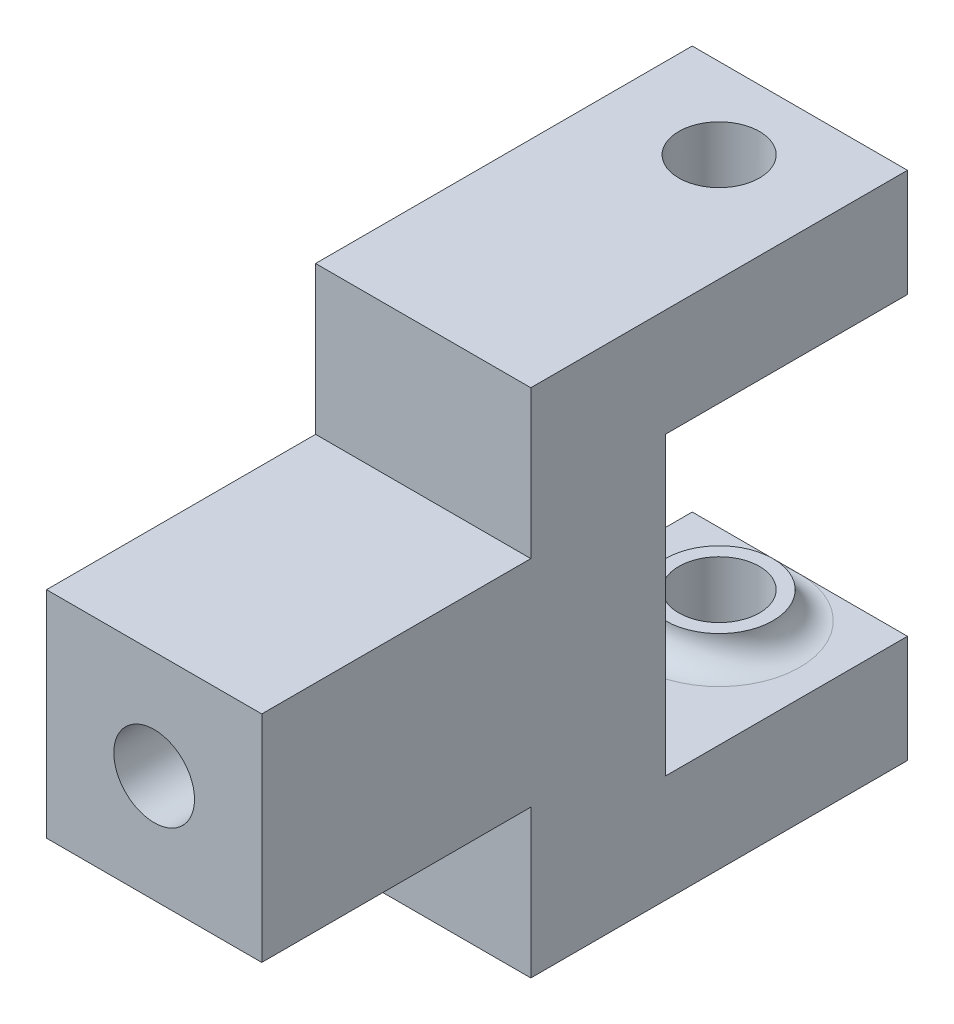
SolidWorks part; units mm, degrees
ref_plane "Спереди" through (0, 0, 0) normal (0, 0, 1) x (1, 0, 0)
ref_plane "Сверху" through (0, 0, 0) normal (0, 1, 0) x (1, 0, 0)
ref_plane "Справа" through (0, 0, 0) normal (1, 0, 0) x (0, 0, -1)
sketch "Эскиз3" plane through (0, 0, 0) normal (1, 0, 0) x (0, 0, -1)
  line L0 (0, 0) -> (14, 0)
  line L1 (14, 0) -> (14, 4)
  line L2 (14, 4) -> (5, 4)
  line L3 (5, 4) -> (5, 15)
  line L4 (5, 15) -> (14, 15)
  line L5 (14, 15) -> (14, 19)
  line L6 (14, 19) -> (0, 19)
  line L7 (0, 19) -> (0, 0)
  dimension "D1" = 4
  dimension "D2" = 4
  dimension "D3" = 11
  dimension "D4" = 9
  dimension "D5" = 5
  dimension "D6" = 14
extrude "Бобышка-Вытянуть1" add sketch "Эскиз3" along normal blind 8
sketch "Эскиз4" plane through (0, 19, 0) normal (0, 1, 0) x (1, 0, 0)
  line L0 (4, 14) -> (4, 0) construction
  line L1 (8, 14) -> (0, 14) construction
  line L2 (8, 0) -> (0, 0) construction
  circle A0 centre (4, 11) radius 1.5
  dimension "D2" = 3
  dimension "D1" = 3
extrude "Вырез-Вытянуть1" cut sketch "Эскиз4" against normal up to surface (19 mm away) up to face at (4, 0, -7)
sketch "Эскиз5" plane through (0, 4, 0) normal (0, 1, 0) x (1, 0, 0)
  circle A0 centre (4, 11) radius 2
  circle A1 centre (4, 11) radius 1.5
  dimension "D1" = 4
  dimension "D2" = 3
extrude "Бобышка-Вытянуть2" add sketch "Эскиз5" along normal blind 1
sketch "Эскиз6" plane through (0, 15, 0) normal (0, -1, 0) x (-1, 0, 0)
  circle A0 centre (-4, 11) radius 2
  circle A1 centre (-4, 11) radius 1.5
  dimension "D1" = 4
  dimension "D2" = 3
extrude "Бобышка-Вытянуть3" add sketch "Эскиз6" along normal blind 1
fillet "Скругление1" radius 1 1 edges at (4, 4, -13)
fillet "Скругление2" radius 1 1 edges at (4, 15, -9)
sketch "Эскиз10" plane through (0, 0, 0) normal (0, 0, 1) x (1, 0, 0)
  line L0 (8, 13.5) -> (0, 13.5)
  line L1 (8, 19) -> (8, 0) construction
  line L2 (0, 19) -> (0, 0) construction
  line L3 (0, 13.5) -> (0, 5.5)
  line L4 (0, 5.5) -> (8, 5.5)
  line L5 (8, 5.5) -> (8, 13.5)
  line L6 (4, 19) -> (4, 0) construction
  line L7 (8, 19) -> (0, 19) construction
  line L8 (8, 0) -> (0, 0) construction
  line L9 (2.2308, 9.5) -> (5.8965, 9.5) construction
  dimension "D1" = 8
extrude "Бобышка-Вытянуть5" add sketch "Эскиз10" along normal blind 10
sketch "Эскиз7" plane through (0, 0, -5) normal (0, 0, -1) x (-1, 0, 0)
  line L0 (-8, 9.5) -> (0, 9.5) construction
  line L1 (-8, 4) -> (-8, 15) construction
  line L2 (0, 4) -> (0, 15) construction
  line L3 (-4, 15) -> (-4, 4) construction
  line L4 (-8, 15) -> (0, 15) construction
  line L5 (-8, 4) -> (0, 4) construction
  circle A0 centre (-4, 9.5) radius 1.5
  dimension "D1" = 3
extrude "Вырез-Вытянуть2" cut sketch "Эскиз7" against normal up to surface (15 mm away) up to face at (4, 9.5, 10)
sketch "Эскиз9" plane through (0, 0, -5) normal (0, 0, -1) x (-1, 0, 0)
  line L1 (-1.2641, 11.1119) -> (-4.028, 12.6753)
  line L2 (-4.028, 12.6753) -> (-6.7639, 11.0634)
  line L3 (-6.7639, 11.0634) -> (-6.7359, 7.8881)
  line L4 (-6.7359, 7.8881) -> (-3.972, 6.3247)
  line L5 (-3.972, 6.3247) -> (-1.2361, 7.9366)
  line L6 (-1.2361, 7.9366) -> (-1.2641, 11.1119)
  circle A0 centre (-4, 9.5) radius 2.75 construction
  dimension "D1" = 5.5
extrude "Вырез-Вытянуть3" cut sketch "Эскиз9" against normal offset from surface (11 mm away) 4 up to face at (5.5, 9.5, 10)
